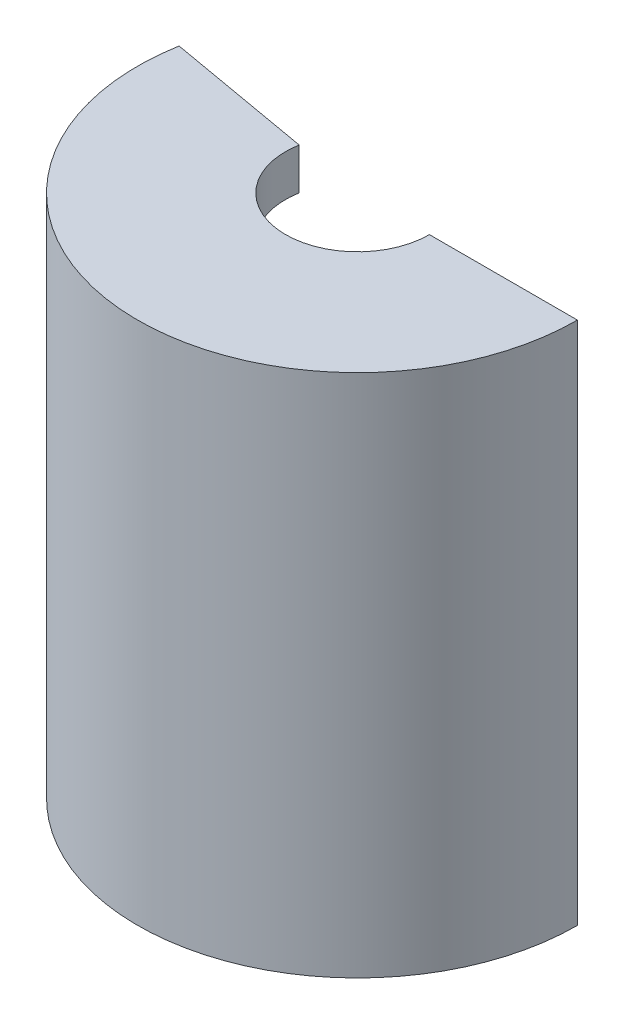
SolidWorks part; units mm, degrees
ref_plane "Front Plane" through (0, 0, 0) normal (0, 0, 1) x (1, 0, 0)
ref_plane "Top Plane" through (0, 0, 0) normal (0, 1, 0) x (1, 0, 0)
ref_plane "Right Plane" through (0, 0, 0) normal (1, 0, 0) x (0, 0, -1)
sketch "Sketch1" plane through (0, 0, 0) normal (0, 0, 1) x (1, 0, 0)
  line L0 (5.2, 99.643) -> (12.8971, 99.643)
  line L1 (12.8971, 99.643) -> (12.8971, 77.4)
  line L2 (12.8971, 77.4) -> (9.725, 77.4)
  line L3 (9.725, 77.4) -> (9.725, 67.748)
  line L4 (9.725, 67.748) -> (2.7, 67.748)
  line L5 (2.7, 67.748) -> (2.7, 64.748)
  line L6 (2.7, 64.748) -> (15.8971, 64.748)
  line L7 (15.8971, 64.748) -> (15.8971, 102.643)
  line L8 (15.8971, 102.643) -> (5.2, 102.643)
  line L9 (5.2, 102.643) -> (5.2, 99.643)
  line L10 (12.1887, 99.543) -> (-12.1584, 99.543) construction
  line L11 (-9.1223, 67.848) -> (9.1425, 67.848) construction
  line L12 (6.6833, 77.5) -> (11.6955, 77.5) construction
  line L13 (9.525, 68.229) -> (9.525, 77.119) construction
  line L14 (12.6971, 91.5674) -> (12.6971, 99.035) construction
  line L15 (5, 86.6812) -> (5, 346.6812) construction
  line L17 (2.5, 55) -> (2.5, 77.2) construction
  dimension "D1" = 0.1
  dimension "D2" = 0.1
  dimension "D3" = 0.1
  dimension "D4" = 0.2
  dimension "D5" = 0.2
  dimension "D6" = 3
  dimension "D7" = 3
  dimension "D8" = 3
  dimension "D9" = 0.2
  dimension "D10" = 0.2
ref_axis "Axis1" through (0, 104.5377, 0) along (0, -1, 0)
revolve "Revolve1" add sketch "Sketch1" angle 190 about axis through (0, 104.5377, 0) along (0, -1, 0) region at (5.6013, 101.143, 0)
